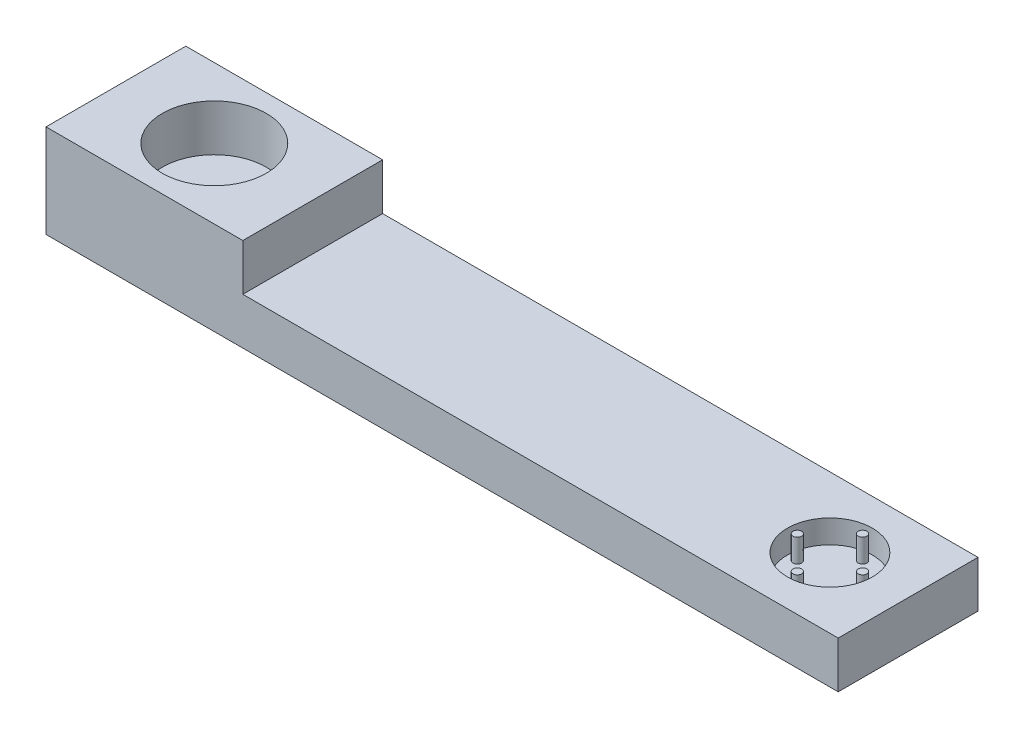
SolidWorks part; units mm, degrees
ref_plane "Front Plane" through (0, 0, 0) normal (0, 0, 1) x (1, 0, 0)
ref_plane "Top Plane" through (0, 0, 0) normal (0, 1, 0) x (1, 0, 0)
ref_plane "Right Plane" through (0, 0, 0) normal (1, 0, 0) x (0, 0, -1)
sketch "Sketch1" plane through (0, 0, 0) normal (0, 1, 0) x (1, 0, 0)
  line L1 (-85, -15) -> (85, -15)
  line L2 (-85, -15) -> (-85, 15)
  line L3 (-85, 15) -> (85, 15)
  line L4 (85, -15) -> (85, 15)
  line L5 (-85, -15) -> (85, 15) construction
  line L6 (-85, 15) -> (85, -15) construction
  point P0 (0, 0)
  dimension "D1" = 170
  dimension "D2" = 30
extrude "Boss-Extrude1" add sketch "Sketch1" along normal blind 10
sketch "Sketch2" plane through (0, 10, 0) normal (0, 1, 0) x (1, 0, 0)
  line L0 (-5.5, 0) -> (5.5, 0) construction
  line L2 (-42.7629, -15) -> (-85, -15)
  line L3 (-42.7629, -15) -> (-42.7629, 15)
  line L4 (-42.7629, 15) -> (-85, 15)
  line L5 (-85, -15) -> (-85, 15)
  line L6 (-42.7629, -15) -> (-85, 15) construction
  line L7 (-42.7629, 15) -> (-85, -15) construction
  circle A1 centre (-63.8815, 0) radius 11.15
  line M3 (85, 15) -> (-85, 15)
  line M4 (-85, 15) -> (-85, -15)
  line M5 (-85, -15) -> (85, -15)
  dimension "D2" = 22.3
extrude "Boss-Extrude3" add sketch "Sketch2" along normal blind 10 contours L3 A1 M5 M3 M4 region at (-63.8815, 10, 14.4819)
sketch "Sketch4" plane through (0, 10, 0) normal (0, 1, 0) x (1, 0, 0)
  line L0 (-11, 0) -> (11, 0) construction
  circle A0 centre (68.2216, 0) radius 9.1
  point P2 (67.1366, 0)
  point P5 (69.8491, 0)
  point P6 (0, 0)
  point P7 (68.2216, 0)
  dimension "D1" = 18.2
extrude "Cut-Extrude1" cut sketch "Sketch4" against normal blind 5
sketch "Sketch5" plane through (0, 5, 0) normal (0, 1, 0) x (1, 0, 0)
  line L0 (-11, 0) -> (11, 0) construction
  circle A0 centre (68.2216, 0) radius 7 construction
  circle A1 centre (68.2216, 7) radius 0.925
  circle A2 centre (68.2216, -7) radius 0.925
  circle A3 centre (61.2216, 0) radius 0.925
  circle A4 centre (75.2216, 0) radius 0.925
  point P7 (68.4514, -7.0003)
  point P8 (0, 0)
  point P9 (0, 0)
  point P10 (68.2216, -4.1899)
  point P11 (0, 0)
  point P14 (61.7612, 0)
  point P17 (61.9445, 0)
  point P20 (74.744, 0)
  dimension "D1" = 14
  dimension "D2" = 1.85
  dimension "D3" = 1.85
extrude "Boss-Extrude4" add sketch "Sketch5" along normal blind 5
